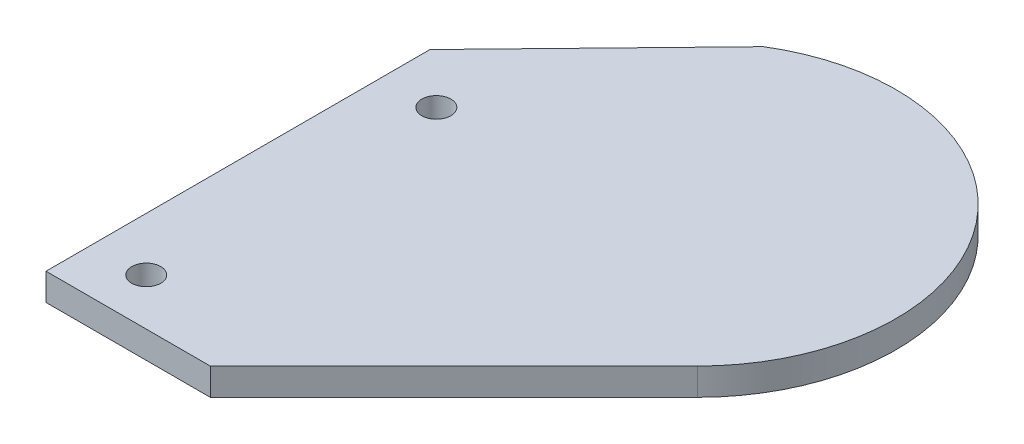
SolidWorks part; units mm, degrees
ref_plane "Front Plane" through (0, 0, 0) normal (0, 0, 1) x (1, 0, 0)
ref_plane "Top Plane" through (0, 0, 0) normal (0, 1, 0) x (1, 0, 0)
ref_plane "Right Plane" through (0, 0, 0) normal (1, 0, 0) x (0, 0, -1)
sketch "Sketch2" plane through (0, 0, 0) normal (0, 1, 0) x (1, 0, 0)
  line L0 (38.5109, 129.6827) -> (38.5109, 0) construction
  line L1 (0, 0) -> (38.5109, 0)
  line L2 (0, 0) -> (0, 90)
  line L3 (0, 129.6827) -> (38.5109, 129.6827) construction
  line L6 (95.6305, 57.1195) -> (38.5109, 0)
  line L8 (0, 129.6827) -> (0, 90) construction
  line L9 (0, 90) -> (62.75, 90) construction
  line L10 (0, 90) -> (38.5109, 129.6827)
  arc A1 (38.5109, 129.6827) -> (95.6305, 57.1195) centre (62.75, 90) cw
  dimension "D1" = 90
  dimension "D3" = 46.5
  dimension "D2" = 62.75
  dimension "D5" = 45
base flange "Base-Flange1" sketch "Sketch2" thickness 6.35 reverse thickness direction no parameters "D1"=0.7366
sketch "Sketch8" plane through (0, 0, 0) normal (0, 1, 0) x (1, 0, 0)
  line L1 (0, 90) -> (0, 0) construction
  line L2 (0, 45) -> (67.0707, 45) construction
  line L3 (0, 90) -> (109.25, 90) construction
  line L4 (67.0707, 28.5598) -> (67.0707, 90) construction
  line L5 (38.5109, 0) -> (95.6305, 57.1195) construction
  line L6 (0, 90) -> (0, 0) construction
  circle A1 centre (12.5, 79) radius 3.4
  circle A3 centre (12.5, 11) radius 3.4
  arc A4 (95.6305, 57.1195) -> (38.5109, 129.6827) centre (62.75, 90) ccw construction
  dimension "D1" = 6.8
  dimension "D3" = 12.5
  dimension "D2" = 11
extrude "Cut-Extrude1" cut sketch "Sketch8" against normal through all normal cut yes
sketch "Bend-Lines1" [suppressed] plane through (0, 0, 0) normal (0, 1, 0) x (1, 0, 0)
sketch "Bounding-Box1" [suppressed] plane through (0, 0, 0) normal (0, 1, 0) x (1, 0, 0)
sheet metal parameters "Sheet-Metal1" thickness 6.35 parameters "D1"=0.7366
flat pattern "Flat-Pattern1" [suppressed]
sketch "Bend-Lines2" plane through (0, 0, 0) normal (0, 1, 0) x (1, 0, 0)
sketch3d "Bounding-Box2" [suppressed]
  line L0 (37.25, -37.25, 0) -> (37.25, 37.25, 0) construction
  line L1 (-22.5, -37.25, 0) -> (-22.5, 37.25, 0) construction
  line L2 (37.25, -37.25, 0) -> (-22.5, -37.25, 0) construction
  line L3 (37.25, 37.25, 0) -> (-22.5, 37.25, 0) construction
sheet metal parameters "Sheet-Metal2" thickness 6.35 parameters "D1"=0.7366
flat pattern "Flat-Pattern1"
sketch "Bend-Lines2" plane through (0, 0, 0) normal (0, 1, 0) x (1, 0, 0)
sketch3d "Bounding-Box2" [suppressed]
  line L0 (-107.7298, -46.3484, 0) -> (0.0689, 64.7304, 0) construction
  line L1 (-42.0452, -110.0934, 0) -> (65.7535, 0.9853, 0) construction
  line L2 (-107.7298, -46.3484, 0) -> (-42.0452, -110.0934, 0) construction
  line L3 (0.0689, 64.7304, 0) -> (65.7535, 0.9853, 0) construction
equation "\"L1L\"=500"
equation "\"L1Thick\"=6.35"
equation "\"Harm-Drive-Outer\"=74.5"
equation "\"L1-Spacing\"=110"
equation "\"L-Bracket-HoleToWall\"=12.5"
equation "\"Bracket-Hole-D\"=6.8"
equation "\"D1@Sketch8\"=\"Bracket-Hole-D\""
equation "\"L-Bracket-HoleToSide\"=11"
equation "\"D3@Sketch8\"=\"L-Bracket-HoleToWall\""
equation "\"D2@Sketch8\"=\"L-Bracket-HoleToSide\""
